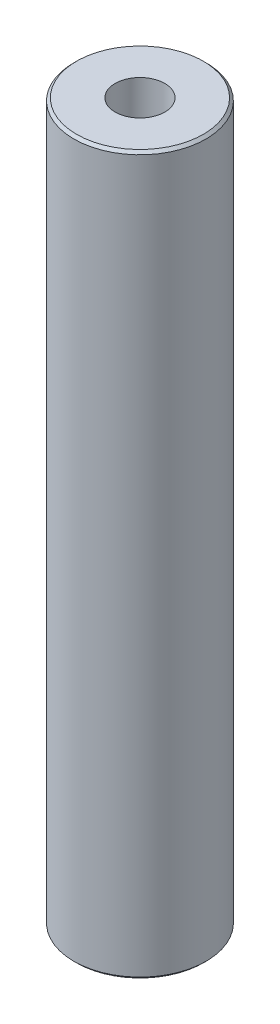
SolidWorks part; units mm, degrees
ref_plane "Front Plane" through (0, 0, 0) normal (0, 0, 1) x (1, 0, 0)
ref_plane "Top Plane" through (0, 0, 0) normal (0, 1, 0) x (1, 0, 0)
ref_plane "Right Plane" through (0, 0, 0) normal (1, 0, 0) x (0, 0, -1)
sketch "Sketch1" plane through (0, 0, 0) normal (0, 1, 0) x (1, 0, 0)
  circle A0 centre (0, 0) radius 52.5
  dimension "SHAFT_OD" = 105
extrude "Boss-Extrude1" add sketch "Sketch1" along normal blind 570.0479
sketch "Sketch2" plane through (0, 0, 0) normal (0, 1, 0) x (1, 0, 0)
  circle A0 centre (0, 0) radius 19.7284
  dimension "BORE_D" = 39.4568
extrude "Cut-Extrude1" cut sketch "Sketch2" along normal through all
chamfer "Chamfer1" distance 2.1421 angle 45 2 edges at (0, 570.0479, 52.5) (0, 0, 52.5)
